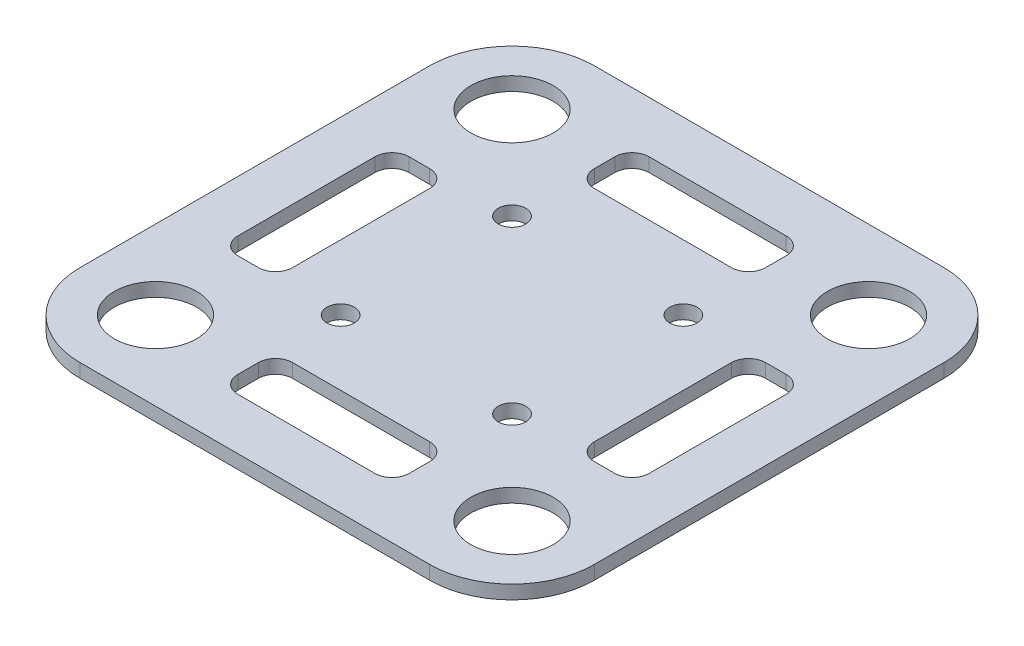
SolidWorks part; units mm, degrees
ref_plane "前视基准面" through (0, 0, 0) normal (0, 0, 1) x (1, 0, 0)
ref_plane "上视基准面" through (0, 0, 0) normal (0, 1, 0) x (1, 0, 0)
ref_plane "右视基准面" through (0, 0, 0) normal (1, 0, 0) x (0, 0, -1)
sketch "草图1" plane through (0, 0, 0) normal (0, 1, 0) x (1, 0, 0)
  line L0 (22, -12.5) -> (30, -12.5)
  line L1 (37.5, -37.5) -> (-37.5, -37.5)
  line L2 (37.5, -37.5) -> (37.5, 37.5)
  line L3 (37.5, 37.5) -> (-37.5, 37.5)
  line L4 (-37.5, -37.5) -> (-37.5, 37.5)
  line L5 (37.5, -37.5) -> (-37.5, 37.5) construction
  line L6 (37.5, 37.5) -> (-37.5, -37.5) construction
  line L11 (15, -15) -> (-15, 15) construction
  line L12 (15, 15) -> (-15, -15) construction
  line L13 (12.5, 22) -> (-12.5, 22)
  line L14 (12.5, 22) -> (12.5, 30)
  line L15 (12.5, 30) -> (-12.5, 30)
  line L16 (-12.5, 22) -> (-12.5, 30)
  line L17 (12.5, 22) -> (-12.5, 30) construction
  line L18 (12.5, 30) -> (-12.5, 22) construction
  line L23 (22, -12.5) -> (22, 12.5)
  line L24 (22, 12.5) -> (30, 12.5)
  line L29 (30, -12.5) -> (30, 12.5)
  line L30 (-12.5, -22) -> (-12.5, -30)
  line L35 (-12.5, -22) -> (12.5, -22)
  line L36 (12.5, -22) -> (12.5, -30)
  line L37 (-12.5, -30) -> (12.5, -30)
  line L38 (-22, 12.5) -> (-30, 12.5)
  line L39 (-22, 12.5) -> (-22, -12.5)
  line L40 (-22, -12.5) -> (-30, -12.5)
  line L41 (-30, 12.5) -> (-30, -12.5)
  circle A0 centre (26, 26) radius 6
  circle A1 centre (26, -26) radius 6
  circle A2 centre (-26, -26) radius 6
  circle A3 centre (-26, 26) radius 6
  circle A4 centre (26, 26) radius 9.5 construction
  circle A5 centre (-12.5, 12.5) radius 2
  circle A6 centre (12.5, 12.5) radius 2
  circle A7 centre (12.5, -12.5) radius 2
  circle A8 centre (-12.5, -12.5) radius 2
  point P0 (0, 0)
  point P6 (0, 0)
  point P11 (0, 26)
  point P31 (0, 0)
  point P40 (0, 0)
  point P49 (0, 0)
  dimension "D9" = 12
  dimension "D11" = 19
  dimension "D12" = 4
  dimension "D1" = 75
  dimension "D2" = 75
  dimension "D3" = 4
  dimension "D4" = 25
  dimension "D5" = 25
  dimension "D6" = 8
  dimension "D7" = 7.5
  dimension "D8" = 4
  dimension "D10" = 4
base flange "基体-法兰1" sketch "草图1" thickness 2 reverse thickness direction no parameters "D1"=0.7366
fillet "圆角1" radius 12 4 edges at (37.5, -1, -37.5) (37.5, -1, 37.5) (-37.5, -1, 37.5) (-37.5, -1, -37.5)
fillet "圆角2" radius 2.5 16 edges at (30, -1, -12.5) (22, -1, -12.5) (30, -1, 12.5) (22, -1, 12.5) (12.5, -1, 22) (12.5, -1, 30) (-12.5, -1, 22) (-12.5, -1, 30) (-22, -1, 12.5) (-30, -1, 12.5) (-22, -1, -12.5) (-30, -1, -12.5) (12.5, -1, -22) (12.5, -1, -30) (-12.5, -1, -22) (-12.5, -1, -30)
sketch "折弯-线1" plane through (0, 0, 0) normal (0, 1, 0) x (1, 0, 0)
sketch "边界框1" plane through (0, 0, 0) normal (0, 1, 0) x (1, 0, 0)
sheet metal parameters "钣金7" thickness 2 parameters "D1"=0.7366
flat pattern "平板型式7" [suppressed]
sketch "折弯-线2" plane through (0, 0, 0) normal (0, 1, 0) x (1, 0, 0)
sketch "边界框2" [suppressed] plane through (0, 0, 0) normal (0, 1, 0) x (1, 0, 0)
